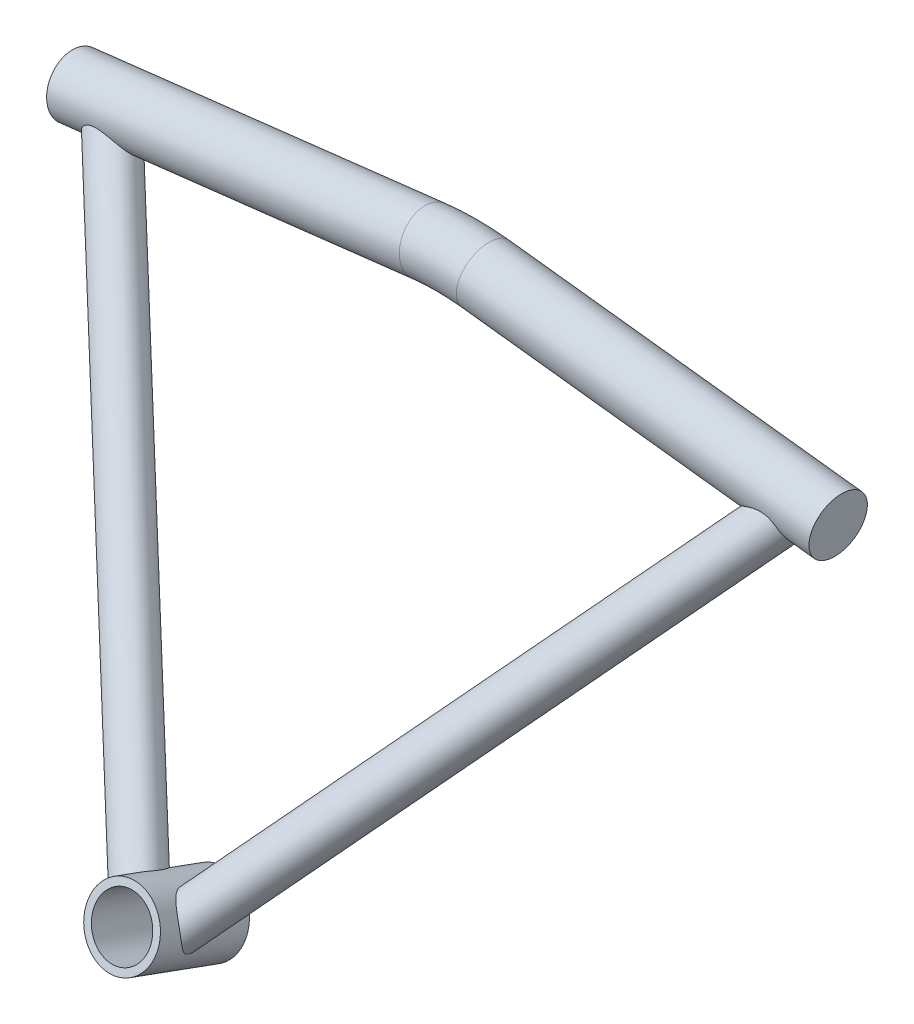
SolidWorks part; units mm, degrees
material "AISI 4130 Steel, normalized at 870C"
ref_plane "Front Plane" through (0, 0, 0) normal (0, 0, 1) x (1, 0, 0)
ref_plane "Top Plane" through (0, 0, 0) normal (0, 1, 0) x (1, 0, 0)
ref_plane "Right Plane" through (0, 0, 0) normal (1, 0, 0) x (0, 0, -1)
sketch "Sketch3" plane through (0, 0, 0) normal (0, 1, 0) x (1, 0, 0)
  line L0 (-5.08, -6.35) -> (5.08, -6.35) construction
  line L2 (0, -88.2205) -> (0, 88.2205) construction
  line L3 (5.08, 0) -> (-5.08, 0) construction
  dimension "D1" = 5.08
  dimension "D2" = 10.16
  dimension "D3" = 6.35
  dimension "D4" = 10.16
  dimension "D5" = 5.08
ref_plane "Plane1" through (0, 3.0807, 3.9431) normal (0, 0.6157, 0.788) x (1, 0, 0)
ref_plane "Plane3" through (0, 0, 0) normal (0, 0.342, 0.9397) x (-1, 0, 0)
sketch "Sketch1" plane through (0, 0, 0) normal (0, 0.342, 0.9397) x (1, 0, 0)
  circle A0 centre (0, 0) radius 15.875
  dimension "D1" = 31.75
extrude "Boss-Extrude1" add sketch "Sketch1" along normal mid plane 41.402 contours A0
sketch "Sketch4" plane through (0, 3.0807, 3.9431) normal (0, 0.6157, 0.788) x (1, 0, 0)
  line L0 (-5.08, -3.9095) -> (-154.2167, 217.1949)
  line L2 (0, -90.5202) -> (0, 90.5202) construction
  dimension "D2" = 34
  dimension "D3" = 266.7
sweep "Sweep1" add path "Sketch4" circular profile diameter 19.05 parameters "D3"=19.05
sketch "Sketch15" plane through (0, 3.0807, 3.9431) normal (0, 0.6157, 0.788) x (1, 0, 0)
  line L0 (5.08, -3.9095) -> (154.2167, 217.1949)
  line L1 (0, -90.5202) -> (0, 90.5202) construction
  dimension "D1" = 266.7
  dimension "D2" = 34
sweep "Sweep2" add path "Sketch15" circular profile diameter 19.05 parameters "D3"=19.05
sketch "Sketch36" plane through (-148.9129, 173.971, -135.9211) normal (-0.5592, 0.6533, -0.5104) x (0.8289, 0.4282, -0.36)
  circle A0 centre (-6.4965, -4.8749) radius 7.9375
  dimension "D1" = 15.875
extrude "Cut-Extrude2" cut sketch "Sketch36" against normal up to surface (276.6627 mm away) up to face at (15.3187, -2.4813, 5.3626)
sketch "Sketch37" plane through (148.9129, 173.971, -135.9211) normal (0.5592, 0.6533, -0.5104) x (0.8289, -0.4282, 0.36)
  circle A0 centre (6.4965, -4.8749) radius 7.9375
  dimension "D1" = 15.875
extrude "Cut-Extrude3" cut sketch "Sketch37" against normal up to surface (252.1455 mm away) up to face at (10.3406, -6.3305, 17.8251)
sketch "Sketch77" plane through (0, 7.0802, 19.4526) normal (0, 0.342, 0.9397) x (1, 0, 0)
  circle A1 centre (0, 0) radius 15.875
extrude "Boss-Extrude2" add sketch "Sketch77" against normal up to surface (41.402 mm away) up to face at (0, -21.9978, -14.023)
sketch "Sketch2" plane through (0, -7.0802, -19.4526) normal (0, -0.342, -0.9397) x (-1, 0, 0)
  circle A0 centre (0, 0) radius 12.7
  dimension "D1" = 25.4
extrude "Cut-Extrude1" cut sketch "Sketch2" against normal up to next
ref_plane "Plane2" through (0, 0, -127) normal (0, 0, 1) x (1, 0, 0)
sketch "Sketch40" plane through (-106.934, 0, -127) normal (0, 0, 1) x (1, 0, 0)
  line L2 (106.934, -90.5202) -> (106.934, 90.5202) construction
  line L3 (94.4829, 187.4611) -> (-59.7307, 169.3775)
  line L4 (119.3851, 187.4611) -> (273.5987, 169.3775)
  arc A0 (94.4829, 187.4611) -> (119.3851, 187.4611) centre (106.934, 81.28) cw
  point P0 (106.934, 188.1886)
  point P7 (106.934, 188.1886)
  dimension "D1" = 155.2702
  dimension "D3" = 106.9086
  dimension "D2" = 155.2702
  dimension "D4" = 7.6
  dimension "D5" = 106.9086
sweep "Sweep3" add path "Sketch40" circular profile diameter 25.4 parameters "D3"=25.4
